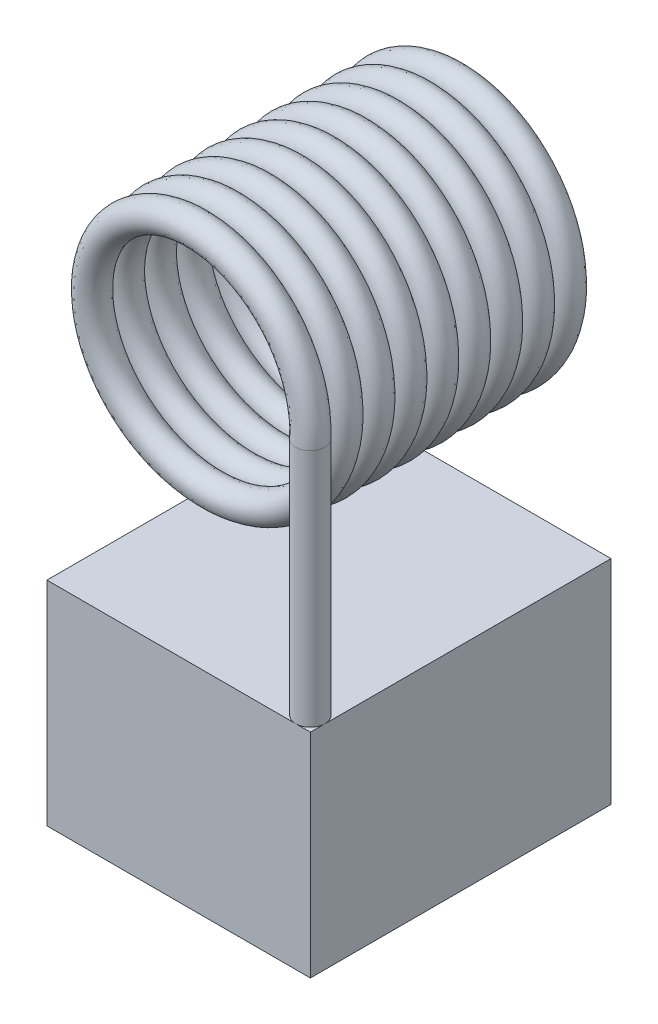
SolidWorks part; units mm, degrees
ref_plane "Front Plane" through (0, 0, 0) normal (0, 0, 1) x (1, 0, 0)
ref_plane "Top Plane" through (0, 0, 0) normal (0, 1, 0) x (1, 0, 0)
ref_plane "Right Plane" through (0, 0, 0) normal (1, 0, 0) x (0, 0, -1)
sketch "Sketch1" plane through (0, 0, 0) normal (0, 0, 1) x (1, 0, 0)
  line L5 (38.5919, -38.5919) -> (-39.5131, 39.5131) construction
  line L6 (38.5864, 38.5864) -> (-38.5864, -38.5864) construction
  circle A0 centre (0, 0) radius 55.88
  point P0 (0, 0)
  dimension "D3" = 111.76
curve "Helix/Spiral1" pitch 15.24 height 129.54 radius 55.88 left hand yes centre (0, 0, 0) axis (0, 0, 1) start towards (-1, 0, 0)
sketch "Sketch2" plane through (0, 0, 0) normal (0, 1, 0) x (1, 0, 0)
  circle A0 centre (-55.88, 0) radius 6.985
  spline S0 degree 3 poles (-55.88, 0) (-55.88, -0.1529) (-55.2099, -0.4595) (-52.2305, -0.9187) (-47.3832, -1.3781) (-40.8416, -1.8374) (-32.8394, -2.2968) (-23.6629, -2.7562) (-13.6402, -3.2155) (-3.1297, -3.6749) (7.4927, -4.1343) (17.8472, -4.5936) (27.5634, -5.053) (36.294, -5.5123) (43.7267, -5.9717) (49.5957, -6.4311) (53.6911, -6.8904) (55.8666, -7.3498) (56.0442, -7.8091) (54.2177, -8.2685) (50.4523, -8.7279) (44.8828, -9.1872) (37.7082, -9.6466) (29.1852, -10.106) (19.6185, -10.5653) (9.3502, -11.0247) (-1.2524, -11.484) (-11.8103, -11.9434) (-21.9458, -12.4028) (-31.2965, -12.8621) (-39.528, -13.3215) (-46.346, -13.7809) (-51.5067, -14.2402) (-54.8255, -14.6996) (-56.1837, -15.1589) (-55.5327, -15.6183) (-52.8959, -16.0777) (-48.3675, -16.537) (-42.1095, -16.9964) (-34.3456, -17.4557) (-25.3536, -17.9151) (-15.4548, -18.3745) (-5.0034, -18.8338) (5.6269, -19.2932) (16.056, -19.7526) (25.9109, -20.2119) (34.8393, -20.6713) (42.5218, -21.1306) (48.6837, -21.59) (53.1046, -22.0494) (55.6265, -22.5087) (56.1592, -22.9681) (54.6837, -23.4274) (51.2526, -23.8868) (45.9887, -24.3462) (39.0803, -24.8055) (30.7743, -25.2649) (21.3678, -25.7243) (11.1972, -26.1836) (0.6262, -26.643) (-9.9672, -27.1023) (-20.2041, -27.5617) (-29.7186, -28.0211) (-38.1703, -28.4804) (-45.257, -28.9398) (-50.7254, -29.3991) (-54.3798, -29.8585) (-56.0895, -30.3179) (-55.7935, -30.7772) (-53.5023, -31.2366) (-49.2978, -31.696) (-43.3304, -32.1553) (-35.8135, -32.6147) (-27.0159, -33.074) (-17.2522, -33.5334) (-6.8716, -33.9928) (3.7548, -34.4521) (14.2468, -34.9115) (24.2295, -35.3709) (33.3456, -35.8302) (41.2693, -36.2896) (47.7173, -36.7489) (52.4588, -37.2083) (55.3244, -37.6677) (56.2116, -38.127) (55.0886, -38.5864) (51.9956, -39.0457) (47.0433, -39.5051) (40.4087, -39.9645) (32.3291, -40.4238) (23.0933, -40.8832) (13.0318, -41.3426) (2.5042, -41.8019) (-8.1129, -42.2613) (-18.4399, -42.7206) (-28.1075, -43.18) (-36.77, -43.6394) (-44.1175, -44.0987) (-49.8874, -44.5581) (-53.8733, -45.0174) (-55.9327, -45.4768) (-55.9919, -45.9362) (-54.0489, -46.3955) (-50.173, -46.8549) (-44.5029, -47.3143) (-37.2414, -47.7736) (-28.6481, -48.233) (-19.0304, -48.6923) (-8.7321, -49.1517) (1.8784, -49.6111) (12.4218, -50.0704) (22.5209, -50.5298) (31.8147, -50.9891) (39.9708, -51.4485) (46.6976, -51.9079) (51.7544, -52.3672) (54.9604, -52.8266) (56.2011, -53.286) (55.432, -53.7453) (52.6806, -54.2047) (48.0454, -54.664) (41.692, -55.1234) (33.8477, -55.5828) (24.793, -56.0421) (14.8518, -56.5015) (4.3794, -56.9609) (-6.2496, -57.4202) (-16.6551, -57.8796) (-26.4651, -58.3389) (-35.3286, -58.7983) (-42.9287, -59.2577) (-48.9938, -59.717) (-53.3067, -60.1764) (-55.7135, -60.6357) (-56.1279, -61.0951) (-54.5351, -61.5545) (-50.9922, -62.0138) (-45.6257, -62.4732) (-38.6277, -62.9326) (-30.2483, -63.3919) (-20.7873, -63.8513) (-10.5829, -64.3106) (0, -64.77) (10.5829, -65.2294) (20.7873, -65.6887) (30.2483, -66.1481) (38.6277, -66.6074) (45.6257, -67.0668) (50.9922, -67.5262) (54.5351, -67.9855) (56.1279, -68.4449) (55.7135, -68.9043) (53.3067, -69.3636) (48.9938, -69.823) (42.9287, -70.2823) (35.3286, -70.7417) (26.4651, -71.2011) (16.6551, -71.6604) (6.2496, -72.1198) (-4.3794, -72.5791) (-14.8518, -73.0385) (-24.793, -73.4979) (-33.8477, -73.9572) (-41.692, -74.4166) (-48.0454, -74.876) (-52.6806, -75.3353) (-55.432, -75.7947) (-56.2011, -76.254) (-54.9604, -76.7134) (-51.7544, -77.1728) (-46.6976, -77.6321) (-39.9708, -78.0915) (-31.8147, -78.5509) (-22.5209, -79.0102) (-12.4218, -79.4696) (-1.8784, -79.9289) (8.7321, -80.3883) (19.0304, -80.8477) (28.6481, -81.307) (37.2414, -81.7664) (44.5029, -82.2257) (50.173, -82.6851) (54.0489, -83.1445) (55.9919, -83.6038) (55.9327, -84.0632) (53.8733, -84.5226) (49.8874, -84.9819) (44.1175, -85.4413) (36.77, -85.9006) (28.1075, -86.36) (18.4399, -86.8194) (8.1129, -87.2787) (-2.5042, -87.7381) (-13.0318, -88.1974) (-23.0933, -88.6568) (-32.3291, -89.1162) (-40.4087, -89.5755) (-47.0433, -90.0349) (-51.9956, -90.4943) (-55.0886, -90.9536) (-56.2116, -91.413) (-55.3244, -91.8723) (-52.4588, -92.3317) (-47.7173, -92.7911) (-41.2693, -93.2504) (-33.3456, -93.7098) (-24.2295, -94.1691) (-14.2468, -94.6285) (-3.7548, -95.0879) (6.8716, -95.5472) (17.2522, -96.0066) (27.0159, -96.466) (35.8135, -96.9253) (43.3304, -97.3847) (49.2978, -97.844) (53.5023, -98.3034) (55.7935, -98.7628) (56.0895, -99.2221) (54.3798, -99.6815) (50.7254, -100.1409) (45.257, -100.6002) (38.1703, -101.0596) (29.7186, -101.5189) (20.2041, -101.9783) (9.9672, -102.4377) (-0.6262, -102.897) (-11.1972, -103.3564) (-21.3678, -103.8157) (-30.7743, -104.2751) (-39.0803, -104.7345) (-45.9887, -105.1938) (-51.2526, -105.6532) (-54.6837, -106.1126) (-56.1592, -106.5719) (-55.6265, -107.0313) (-53.1046, -107.4906) (-48.6837, -107.95) (-42.5218, -108.4094) (-34.8393, -108.8687) (-25.9109, -109.3281) (-16.056, -109.7874) (-5.6269, -110.2468) (5.0034, -110.7062) (15.4548, -111.1655) (25.3536, -111.6249) (34.3456, -112.0843) (42.1095, -112.5436) (48.3675, -113.003) (52.8959, -113.4623) (55.5327, -113.9217) (56.1837, -114.3811) (54.8255, -114.8404) (51.5067, -115.2998) (46.346, -115.7591) (39.528, -116.2185) (31.2965, -116.6779) (21.9458, -117.1372) (11.8103, -117.5966) (1.2524, -118.056) (-9.3502, -118.5153) (-19.6185, -118.9747) (-29.1852, -119.434) (-37.7082, -119.8934) (-44.8828, -120.3528) (-50.4523, -120.8121) (-54.2177, -121.2715) (-56.0442, -121.7309) (-55.8666, -122.1902) (-53.6911, -122.6496) (-49.5957, -123.1089) (-43.7267, -123.5683) (-36.294, -124.0277) (-27.5634, -124.487) (-17.8472, -124.9464) (-7.4927, -125.4057) (3.1297, -125.8651) (13.6402, -126.3245) (23.6629, -126.7838) (32.8394, -127.2432) (40.8416, -127.7026) (47.3832, -128.1619) (52.2305, -128.6213) (55.2099, -129.0805) (55.88, -129.3871) (55.88, -129.54) knots 0 0 0 0 0.003546 0.007092 0.010638 0.014184 0.01773 0.021277 0.024823 0.028369 0.031915 0.035461 0.039007 0.042553 0.046099 0.049645 0.053191 0.056738 0.060284 0.06383 0.067376 0.070922 0.074468 0.078014 0.08156 0.085106 0.088652 0.092199 0.095745 0.099291 0.102837 0.106383 0.109929 0.113475 0.117021 0.120567 0.124113 0.12766 0.131206 0.134752 0.138298 0.141844 0.14539 0.148936 0.152482 0.156028 0.159574 0.163121 0.166667 0.170213 0.173759 0.177305 0.180851 0.184397 0.187943 0.191489 0.195035 0.198582 0.202128 0.205674 0.20922 0.212766 0.216312 0.219858 0.223404 0.22695 0.230496 0.234043 0.237589 0.241135 0.244681 0.248227 0.251773 0.255319 0.258865 0.262411 0.265957 0.269504 0.27305 0.276596 0.280142 0.283688 0.287234 0.29078 0.294326 0.297872 0.301418 0.304965 0.308511 0.312057 0.315603 0.319149 0.322695 0.326241 0.329787 0.333333 0.336879 0.340426 0.343972 0.347518 0.351064 0.35461 0.358156 0.361702 0.365248 0.368794 0.37234 0.375887 0.379433 0.382979 0.386525 0.390071 0.393617 0.397163 0.400709 0.404255 0.407801 0.411348 0.414894 0.41844 0.421986 0.425532 0.429078 0.432624 0.43617 0.439716 0.443262 0.446809 0.450355 0.453901 0.457447 0.460993 0.464539 0.468085 0.471631 0.475177 0.478723 0.48227 0.485816 0.489362 0.492908 0.496454 0.5 0.503546 0.507092 0.510638 0.514184 0.51773 0.521277 0.524823 0.528369 0.531915 0.535461 0.539007 0.542553 0.546099 0.549645 0.553191 0.556738 0.560284 0.56383 0.567376 0.570922 0.574468 0.578014 0.58156 0.585106 0.588652 0.592199 0.595745 0.599291 0.602837 0.606383 0.609929 0.613475 0.617021 0.620567 0.624113 0.62766 0.631206 0.634752 0.638298 0.641844 0.64539 0.648936 0.652482 0.656028 0.659574 0.663121 0.666667 0.670213 0.673759 0.677305 0.680851 0.684397 0.687943 0.691489 0.695035 0.698582 0.702128 0.705674 0.70922 0.712766 0.716312 0.719858 0.723404 0.72695 0.730496 0.734043 0.737589 0.741135 0.744681 0.748227 0.751773 0.755319 0.758865 0.762411 0.765957 0.769504 0.77305 0.776596 0.780142 0.783688 0.787234 0.79078 0.794326 0.797872 0.801418 0.804965 0.808511 0.812057 0.815603 0.819149 0.822695 0.826241 0.829787 0.833333 0.836879 0.840426 0.843972 0.847518 0.851064 0.85461 0.858156 0.861702 0.865248 0.868794 0.87234 0.875887 0.879433 0.882979 0.886525 0.890071 0.893617 0.897163 0.900709 0.904255 0.907801 0.911348 0.914894 0.91844 0.921986 0.925532 0.929078 0.932624 0.93617 0.939716 0.943262 0.946809 0.950355 0.953901 0.957447 0.960993 0.964539 0.968085 0.971631 0.975177 0.978723 0.98227 0.985816 0.989362 0.992908 0.996454 1 1 1 1 construction
sweep "Sweep1" add profiles "Sketch2" path "Helix/Spiral1"
sketch "Sketch3" plane through (0, 0, 0) normal (0, -1, 0) x (1, 0, 0)
  circle A0 centre (55.88, 129.54) radius 6.985
  circle A1 centre (-55.88, 0) radius 6.985
  spline S0 degree 3 poles (-55.88, 0) (-55.88, 0.1529) (-55.2099, 0.4595) (-52.2305, 0.9187) (-47.3832, 1.3781) (-40.8416, 1.8374) (-32.8394, 2.2968) (-23.6629, 2.7562) (-13.6402, 3.2155) (-3.1297, 3.6749) (7.4927, 4.1343) (17.8472, 4.5936) (27.5634, 5.053) (36.294, 5.5123) (43.7267, 5.9717) (49.5957, 6.4311) (53.6911, 6.8904) (55.8666, 7.3498) (56.0442, 7.8091) (54.2177, 8.2685) (50.4523, 8.7279) (44.8828, 9.1872) (37.7082, 9.6466) (29.1852, 10.106) (19.6185, 10.5653) (9.3502, 11.0247) (-1.2524, 11.484) (-11.8103, 11.9434) (-21.9458, 12.4028) (-31.2965, 12.8621) (-39.528, 13.3215) (-46.346, 13.7809) (-51.5067, 14.2402) (-54.8255, 14.6996) (-56.1837, 15.1589) (-55.5327, 15.6183) (-52.8959, 16.0777) (-48.3675, 16.537) (-42.1095, 16.9964) (-34.3456, 17.4557) (-25.3536, 17.9151) (-15.4548, 18.3745) (-5.0034, 18.8338) (5.6269, 19.2932) (16.056, 19.7526) (25.9109, 20.2119) (34.8393, 20.6713) (42.5218, 21.1306) (48.6837, 21.59) (53.1046, 22.0494) (55.6265, 22.5087) (56.1592, 22.9681) (54.6837, 23.4274) (51.2526, 23.8868) (45.9887, 24.3462) (39.0803, 24.8055) (30.7743, 25.2649) (21.3678, 25.7243) (11.1972, 26.1836) (0.6262, 26.643) (-9.9672, 27.1023) (-20.2041, 27.5617) (-29.7186, 28.0211) (-38.1703, 28.4804) (-45.257, 28.9398) (-50.7254, 29.3991) (-54.3798, 29.8585) (-56.0895, 30.3179) (-55.7935, 30.7772) (-53.5023, 31.2366) (-49.2978, 31.696) (-43.3304, 32.1553) (-35.8135, 32.6147) (-27.0159, 33.074) (-17.2522, 33.5334) (-6.8716, 33.9928) (3.7548, 34.4521) (14.2468, 34.9115) (24.2295, 35.3709) (33.3456, 35.8302) (41.2693, 36.2896) (47.7173, 36.7489) (52.4588, 37.2083) (55.3244, 37.6677) (56.2116, 38.127) (55.0886, 38.5864) (51.9956, 39.0457) (47.0433, 39.5051) (40.4087, 39.9645) (32.3291, 40.4238) (23.0933, 40.8832) (13.0318, 41.3426) (2.5042, 41.8019) (-8.1129, 42.2613) (-18.4399, 42.7206) (-28.1075, 43.18) (-36.77, 43.6394) (-44.1175, 44.0987) (-49.8874, 44.5581) (-53.8733, 45.0174) (-55.9327, 45.4768) (-55.9919, 45.9362) (-54.0489, 46.3955) (-50.173, 46.8549) (-44.5029, 47.3143) (-37.2414, 47.7736) (-28.6481, 48.233) (-19.0304, 48.6923) (-8.7321, 49.1517) (1.8784, 49.6111) (12.4218, 50.0704) (22.5209, 50.5298) (31.8147, 50.9891) (39.9708, 51.4485) (46.6976, 51.9079) (51.7544, 52.3672) (54.9604, 52.8266) (56.2011, 53.286) (55.432, 53.7453) (52.6806, 54.2047) (48.0454, 54.664) (41.692, 55.1234) (33.8477, 55.5828) (24.793, 56.0421) (14.8518, 56.5015) (4.3794, 56.9609) (-6.2496, 57.4202) (-16.6551, 57.8796) (-26.4651, 58.3389) (-35.3286, 58.7983) (-42.9287, 59.2577) (-48.9938, 59.717) (-53.3067, 60.1764) (-55.7135, 60.6357) (-56.1279, 61.0951) (-54.5351, 61.5545) (-50.9922, 62.0138) (-45.6257, 62.4732) (-38.6277, 62.9326) (-30.2483, 63.3919) (-20.7873, 63.8513) (-10.5829, 64.3106) (0, 64.77) (10.5829, 65.2294) (20.7873, 65.6887) (30.2483, 66.1481) (38.6277, 66.6074) (45.6257, 67.0668) (50.9922, 67.5262) (54.5351, 67.9855) (56.1279, 68.4449) (55.7135, 68.9043) (53.3067, 69.3636) (48.9938, 69.823) (42.9287, 70.2823) (35.3286, 70.7417) (26.4651, 71.2011) (16.6551, 71.6604) (6.2496, 72.1198) (-4.3794, 72.5791) (-14.8518, 73.0385) (-24.793, 73.4979) (-33.8477, 73.9572) (-41.692, 74.4166) (-48.0454, 74.876) (-52.6806, 75.3353) (-55.432, 75.7947) (-56.2011, 76.254) (-54.9604, 76.7134) (-51.7544, 77.1728) (-46.6976, 77.6321) (-39.9708, 78.0915) (-31.8147, 78.5509) (-22.5209, 79.0102) (-12.4218, 79.4696) (-1.8784, 79.9289) (8.7321, 80.3883) (19.0304, 80.8477) (28.6481, 81.307) (37.2414, 81.7664) (44.5029, 82.2257) (50.173, 82.6851) (54.0489, 83.1445) (55.9919, 83.6038) (55.9327, 84.0632) (53.8733, 84.5226) (49.8874, 84.9819) (44.1175, 85.4413) (36.77, 85.9006) (28.1075, 86.36) (18.4399, 86.8194) (8.1129, 87.2787) (-2.5042, 87.7381) (-13.0318, 88.1974) (-23.0933, 88.6568) (-32.3291, 89.1162) (-40.4087, 89.5755) (-47.0433, 90.0349) (-51.9956, 90.4943) (-55.0886, 90.9536) (-56.2116, 91.413) (-55.3244, 91.8723) (-52.4588, 92.3317) (-47.7173, 92.7911) (-41.2693, 93.2504) (-33.3456, 93.7098) (-24.2295, 94.1691) (-14.2468, 94.6285) (-3.7548, 95.0879) (6.8716, 95.5472) (17.2522, 96.0066) (27.0159, 96.466) (35.8135, 96.9253) (43.3304, 97.3847) (49.2978, 97.844) (53.5023, 98.3034) (55.7935, 98.7628) (56.0895, 99.2221) (54.3798, 99.6815) (50.7254, 100.1409) (45.257, 100.6002) (38.1703, 101.0596) (29.7186, 101.5189) (20.2041, 101.9783) (9.9672, 102.4377) (-0.6262, 102.897) (-11.1972, 103.3564) (-21.3678, 103.8157) (-30.7743, 104.2751) (-39.0803, 104.7345) (-45.9887, 105.1938) (-51.2526, 105.6532) (-54.6837, 106.1126) (-56.1592, 106.5719) (-55.6265, 107.0313) (-53.1046, 107.4906) (-48.6837, 107.95) (-42.5218, 108.4094) (-34.8393, 108.8687) (-25.9109, 109.3281) (-16.056, 109.7874) (-5.6269, 110.2468) (5.0034, 110.7062) (15.4548, 111.1655) (25.3536, 111.6249) (34.3456, 112.0843) (42.1095, 112.5436) (48.3675, 113.003) (52.8959, 113.4623) (55.5327, 113.9217) (56.1837, 114.3811) (54.8255, 114.8404) (51.5067, 115.2998) (46.346, 115.7591) (39.528, 116.2185) (31.2965, 116.6779) (21.9458, 117.1372) (11.8103, 117.5966) (1.2524, 118.056) (-9.3502, 118.5153) (-19.6185, 118.9747) (-29.1852, 119.434) (-37.7082, 119.8934) (-44.8828, 120.3528) (-50.4523, 120.8121) (-54.2177, 121.2715) (-56.0442, 121.7309) (-55.8666, 122.1902) (-53.6911, 122.6496) (-49.5957, 123.1089) (-43.7267, 123.5683) (-36.294, 124.0277) (-27.5634, 124.487) (-17.8472, 124.9464) (-7.4927, 125.4057) (3.1297, 125.8651) (13.6402, 126.3245) (23.6629, 126.7838) (32.8394, 127.2432) (40.8416, 127.7026) (47.3832, 128.1619) (52.2305, 128.6213) (55.2099, 129.0805) (55.88, 129.3871) (55.88, 129.54) knots 0 0 0 0 0.003546 0.007092 0.010638 0.014184 0.01773 0.021277 0.024823 0.028369 0.031915 0.035461 0.039007 0.042553 0.046099 0.049645 0.053191 0.056738 0.060284 0.06383 0.067376 0.070922 0.074468 0.078014 0.08156 0.085106 0.088652 0.092199 0.095745 0.099291 0.102837 0.106383 0.109929 0.113475 0.117021 0.120567 0.124113 0.12766 0.131206 0.134752 0.138298 0.141844 0.14539 0.148936 0.152482 0.156028 0.159574 0.163121 0.166667 0.170213 0.173759 0.177305 0.180851 0.184397 0.187943 0.191489 0.195035 0.198582 0.202128 0.205674 0.20922 0.212766 0.216312 0.219858 0.223404 0.22695 0.230496 0.234043 0.237589 0.241135 0.244681 0.248227 0.251773 0.255319 0.258865 0.262411 0.265957 0.269504 0.27305 0.276596 0.280142 0.283688 0.287234 0.29078 0.294326 0.297872 0.301418 0.304965 0.308511 0.312057 0.315603 0.319149 0.322695 0.326241 0.329787 0.333333 0.336879 0.340426 0.343972 0.347518 0.351064 0.35461 0.358156 0.361702 0.365248 0.368794 0.37234 0.375887 0.379433 0.382979 0.386525 0.390071 0.393617 0.397163 0.400709 0.404255 0.407801 0.411348 0.414894 0.41844 0.421986 0.425532 0.429078 0.432624 0.43617 0.439716 0.443262 0.446809 0.450355 0.453901 0.457447 0.460993 0.464539 0.468085 0.471631 0.475177 0.478723 0.48227 0.485816 0.489362 0.492908 0.496454 0.5 0.503546 0.507092 0.510638 0.514184 0.51773 0.521277 0.524823 0.528369 0.531915 0.535461 0.539007 0.542553 0.546099 0.549645 0.553191 0.556738 0.560284 0.56383 0.567376 0.570922 0.574468 0.578014 0.58156 0.585106 0.588652 0.592199 0.595745 0.599291 0.602837 0.606383 0.609929 0.613475 0.617021 0.620567 0.624113 0.62766 0.631206 0.634752 0.638298 0.641844 0.64539 0.648936 0.652482 0.656028 0.659574 0.663121 0.666667 0.670213 0.673759 0.677305 0.680851 0.684397 0.687943 0.691489 0.695035 0.698582 0.702128 0.705674 0.70922 0.712766 0.716312 0.719858 0.723404 0.72695 0.730496 0.734043 0.737589 0.741135 0.744681 0.748227 0.751773 0.755319 0.758865 0.762411 0.765957 0.769504 0.77305 0.776596 0.780142 0.783688 0.787234 0.79078 0.794326 0.797872 0.801418 0.804965 0.808511 0.812057 0.815603 0.819149 0.822695 0.826241 0.829787 0.833333 0.836879 0.840426 0.843972 0.847518 0.851064 0.85461 0.858156 0.861702 0.865248 0.868794 0.87234 0.875887 0.879433 0.882979 0.886525 0.890071 0.893617 0.897163 0.900709 0.904255 0.907801 0.911348 0.914894 0.91844 0.921986 0.925532 0.929078 0.932624 0.93617 0.939716 0.943262 0.946809 0.950355 0.953901 0.957447 0.960993 0.964539 0.968085 0.971631 0.975177 0.978723 0.98227 0.985816 0.989362 0.992908 0.996454 1 1 1 1 construction
  point P6 (0, 0)
  point P7 (55.88, 129.54)
extrude "Boss-Extrude1" add sketch "Sketch3" along normal blind 152.4
sketch "Sketch4" plane through (0, -152.4, 0) normal (0, -1, 0) x (1, 0, 0)
  line L1 (62.865, 136.525) -> (-62.865, 136.525)
  line L2 (62.865, 136.525) -> (62.865, -6.985)
  line L3 (62.865, -6.985) -> (-62.865, -6.985)
  line L4 (-62.865, 136.525) -> (-62.865, -6.985)
  circle A0 centre (-55.88, 0) radius 6.985 construction
  circle A1 centre (55.88, 129.54) radius 6.985 construction
extrude "Boss-Extrude2" add sketch "Sketch4" along normal blind 63.5 and the other way blind 38.1
